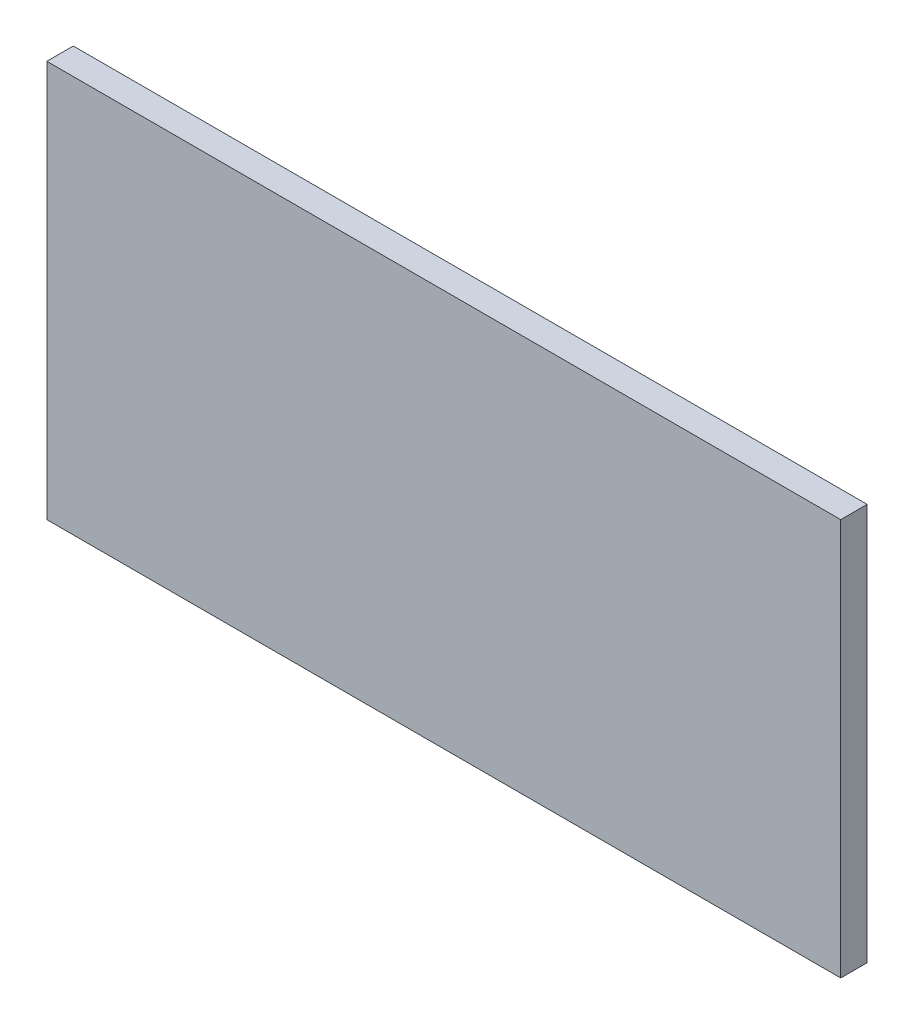
SolidWorks part; units mm, degrees
material "Лист 6,0 ГОСТ 19903-2015 / Ст3сп ГОСТ 14637-89"
ref_plane "Спереди" through (0, 0, 0) normal (0, 0, 1) x (1, 0, 0)
ref_plane "Сверху" through (0, 0, 0) normal (0, 1, 0) x (1, 0, 0)
ref_plane "Справа" through (0, 0, 0) normal (1, 0, 0) x (0, 0, -1)
sketch "Эскиз1" plane through (0, 0, 0) normal (0, 0, 1) x (1, 0, 0)
  line L1 (-90, -45) -> (90, -45)
  line L2 (-90, -45) -> (-90, 45)
  line L3 (-90, 45) -> (90, 45)
  line L4 (90, -45) -> (90, 45)
extrude "Бобышка-Вытянуть1" add sketch "Эскиз1" along normal blind 6
